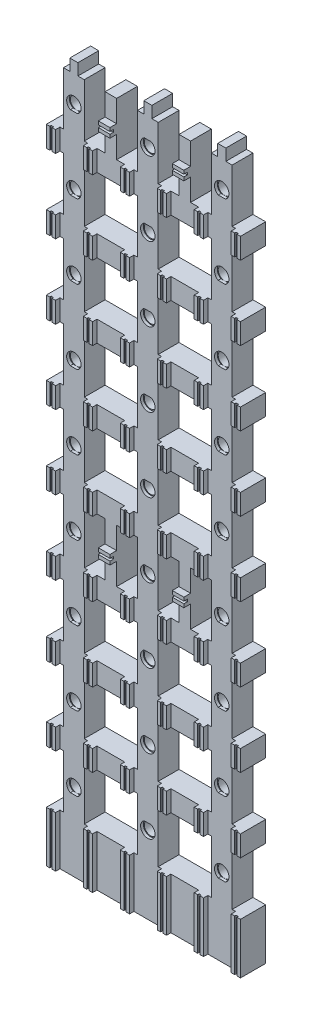
SolidWorks part; units mm, degrees
ref_plane "Front Plane" through (0, 0, 0) normal (0, 0, 1) x (1, 0, 0)
ref_plane "Top Plane" through (0, 0, 0) normal (0, 1, 0) x (1, 0, 0)
ref_plane "Right Plane" through (0, 0, 0) normal (1, 0, 0) x (0, 0, -1)
sketch "Sketch1" plane through (0, 0, 0) normal (0, 0, 1) x (1, 0, 0)
  line L1 (42, -11) -> (-42, -11)
  line L2 (42, -11) -> (42, 11)
  line L3 (42, 11) -> (-42, 11)
  line L4 (-42, -11) -> (-42, 11)
  line L5 (42, -11) -> (-42, 11) construction
  line L6 (42, 11) -> (-42, -11) construction
  point P0 (0, 0)
  dimension "D1" = 22
  dimension "D2" = 84
extrude "Boss-Extrude1" add sketch "Sketch1" along normal blind 9
sketch "Sketch2" plane through (0, 0, 9) normal (0, 0, 1) x (1, 0, 0)
  line L0 (42, 11) -> (-42, 11) construction
  line L1 (-36.5, 11) -> (-27.5, 11)
  line L2 (-36.5, 11) -> (-36.5, 295) construction
  line L3 (-36.5, 295) -> (-27.5, 295) construction
  line L4 (-27.5, 11) -> (-27.5, 295) construction
  line L5 (-42, 11) -> (-42, -11) construction
  line L6 (-33.75, 295) -> (-30.25, 295)
  line L7 (-30.25, 295) -> (-30.25, 290)
  line L8 (-30.25, 290) -> (-27.5, 290)
  line L9 (-27.5, 290) -> (-27.5, 11)
  line L10 (-36.5, 11) -> (-36.5, 290)
  line L11 (-36.5, 290) -> (-33.75, 290)
  line L12 (-33.75, 290) -> (-33.75, 295)
  point P10 (-32, 295)
  point P15 (-32, 11)
  dimension "D1" = 5.5
  dimension "D2" = 9
  dimension "D3" = 284
  dimension "D4" = 5
  dimension "D5" = 3.5
extrude "Boss-Extrude2" add sketch "Sketch2" against normal up to surface (9 mm away) up to face at (0, 0, 0)
pattern_linear "LPattern1" count 3 spacing 32 along (1, 0, 0) of "Boss-Extrude2"
sketch "Sketch3" plane through (0, 0, 9) normal (0, 0, 1) x (1, 0, 0)
  line L0 (-42, 11) -> (-42, -11) construction
  line L1 (-42, 43) -> (42, 43)
  line L2 (-42, 43) -> (-42, 34)
  line L3 (-42, 34) -> (42, 34)
  line L4 (42, 43) -> (42, 34)
  line L5 (42, -11) -> (42, 11) construction
  line L6 (-36.5, 11) -> (-42, 11) construction
  dimension "D1" = 23
  dimension "D2" = 9
extrude "Boss-Extrude3" add sketch "Sketch3" against normal up to surface (9 mm away) up to face at (0, 189.8571, 0)
pattern_linear "LPattern2" count 8 spacing 32 along (0, 1, 0) of "Boss-Extrude3"
sketch "Sketch4" plane through (0, 0, 9) normal (0, 0, 1) x (1, 0, 0)
  line L0 (-27.5, 130) -> (-4.5, 130) construction
  line L1 (-13.5, 130) -> (-18.5, 130)
  line L2 (-13.5, 130) -> (-13.5, 107)
  line L3 (-13.5, 107) -> (-18.5, 107)
  line L4 (-18.5, 130) -> (-18.5, 107)
  line L5 (-4.5, 107) -> (-27.5, 107) construction
  point P8 (-16, 107)
  dimension "D1" = 5
extrude "Boss-Extrude4" add sketch "Sketch4" against normal up to surface (9 mm away) up to face at (-16, 246.5, 0)
pattern_linear "LPattern3" count 2 spacing 32 along (1, 0, 0) count 2 spacing 160 along (0, 1, 0) of "Boss-Extrude4"
sketch "Sketch5" plane through (0, 0, 9) normal (0, 0, 1) x (1, 0, 0)
  line L0 (-36.5, 22.5) -> (-27.5, 22.5) construction
  line L1 (-36.5, 34) -> (-36.5, 11) construction
  line L2 (-27.5, 11) -> (-27.5, 34) construction
  line L3 (-4.5, 22.5) -> (4.5, 22.5) construction
  line L4 (-4.5, 34) -> (-4.5, 11) construction
  line L5 (4.5, 11) -> (4.5, 34) construction
  line L6 (27.5, 22.5) -> (36.5, 22.5) construction
  line L7 (27.5, 34) -> (27.5, 11) construction
  line L8 (36.5, 11) -> (36.5, 34) construction
  circle A0 centre (-32, 22.5) radius 2.725
  circle A1 centre (0, 22.5) radius 2.725
  circle A2 centre (32, 22.5) radius 2.725
  circle A3 centre (-32, 54.5) radius 2.725
  circle A4 centre (0, 54.5) radius 2.725
  circle A5 centre (32, 54.5) radius 2.725
  circle A6 centre (-32, 86.5) radius 2.725
  circle A7 centre (0, 86.5) radius 2.725
  circle A8 centre (32, 86.5) radius 2.725
  circle A9 centre (-32, 118.5) radius 2.725
  circle A10 centre (0, 118.5) radius 2.725
  circle A11 centre (32, 118.5) radius 2.725
  circle A12 centre (-32, 150.5) radius 2.725
  circle A13 centre (0, 150.5) radius 2.725
  circle A14 centre (32, 150.5) radius 2.725
  circle A15 centre (-32, 182.5) radius 2.725
  circle A16 centre (0, 182.5) radius 2.725
  circle A17 centre (32, 182.5) radius 2.725
  circle A18 centre (-32, 214.5) radius 2.725
  circle A19 centre (0, 214.5) radius 2.725
  circle A20 centre (32, 214.5) radius 2.725
  circle A21 centre (-32, 246.5) radius 2.725
  circle A22 centre (0, 246.5) radius 2.725
  circle A23 centre (32, 246.5) radius 2.725
  circle A24 centre (-32, 278.5) radius 2.725
  circle A25 centre (0, 278.5) radius 2.725
  circle A26 centre (32, 278.5) radius 2.725
  dimension "D1" = 5.45
  dimension "D3" = 32
  dimension "D2" = 9
extrude "Cut-Extrude1" cut sketch "Sketch5" against normal through all
sketch "Sketch6" plane through (0, 0, 9) normal (0, 0, 1) x (1, 0, 0)
  line L0 (-33.5297, 19.775) -> (-30.4703, 19.775)
  line L1 (-1.5297, 25.225) -> (1.5297, 25.225)
  line L2 (30.4703, 19.775) -> (33.5297, 19.775)
  line L3 (-33.5297, 51.775) -> (-30.4703, 51.775)
  line L4 (-1.5297, 57.225) -> (1.5297, 57.225)
  line L5 (30.4703, 51.775) -> (33.5297, 51.775)
  line L6 (-33.5297, 83.775) -> (-30.4703, 83.775)
  line L7 (-1.5297, 89.225) -> (1.5297, 89.225)
  line L8 (30.4703, 83.775) -> (33.5297, 83.775)
  line L9 (-33.5297, 115.775) -> (-30.4703, 115.775)
  line L10 (-1.5297, 121.225) -> (1.5297, 121.225)
  line L11 (30.4703, 115.775) -> (33.5297, 115.775)
  line L12 (-33.5297, 147.775) -> (-30.4703, 147.775)
  line L13 (-1.5297, 153.225) -> (1.5297, 153.225)
  line L14 (30.4703, 147.775) -> (33.5297, 147.775)
  line L15 (-33.5297, 179.775) -> (-30.4703, 179.775)
  line L16 (-1.5297, 185.225) -> (1.5297, 185.225)
  line L17 (30.4703, 179.775) -> (33.5297, 179.775)
  line L18 (-33.5297, 211.775) -> (-30.4703, 211.775)
  line L19 (-1.5297, 217.225) -> (1.5297, 217.225)
  line L20 (30.4703, 211.775) -> (33.5297, 211.775)
  line L21 (-33.5297, 243.775) -> (-30.4703, 243.775)
  line L22 (-1.5297, 249.225) -> (1.5297, 249.225)
  line L23 (30.4703, 243.775) -> (33.5297, 243.775)
  line L24 (-33.5297, 275.775) -> (-30.4703, 275.775)
  line L25 (-1.5297, 281.225) -> (1.5297, 281.225)
  line L26 (30.4703, 275.775) -> (33.5297, 275.775)
  arc A0 (-30.4703, 19.775) -> (-33.5297, 19.775) centre (-32, 22.5) ccw
  arc A1 (-1.5297, 25.225) -> (1.5297, 25.225) centre (0, 22.5) ccw
  arc A2 (33.5297, 19.775) -> (30.4703, 19.775) centre (32, 22.5) ccw
  circle A3 centre (32, 22.5) radius 2.725 construction
  circle A4 centre (0, 22.5) radius 2.725 construction
  circle A5 centre (-32, 22.5) radius 2.725 construction
  arc A6 (-30.4703, 51.775) -> (-33.5297, 51.775) centre (-32, 54.5) ccw
  arc A7 (-1.5297, 57.225) -> (1.5297, 57.225) centre (0, 54.5) ccw
  arc A8 (33.5297, 51.775) -> (30.4703, 51.775) centre (32, 54.5) ccw
  arc A9 (-30.4703, 83.775) -> (-33.5297, 83.775) centre (-32, 86.5) ccw
  arc A10 (-1.5297, 89.225) -> (1.5297, 89.225) centre (0, 86.5) ccw
  arc A11 (33.5297, 83.775) -> (30.4703, 83.775) centre (32, 86.5) ccw
  arc A12 (-30.4703, 115.775) -> (-33.5297, 115.775) centre (-32, 118.5) ccw
  arc A13 (-1.5297, 121.225) -> (1.5297, 121.225) centre (0, 118.5) ccw
  arc A14 (33.5297, 115.775) -> (30.4703, 115.775) centre (32, 118.5) ccw
  arc A15 (-30.4703, 147.775) -> (-33.5297, 147.775) centre (-32, 150.5) ccw
  arc A16 (-1.5297, 153.225) -> (1.5297, 153.225) centre (0, 150.5) ccw
  arc A17 (33.5297, 147.775) -> (30.4703, 147.775) centre (32, 150.5) ccw
  arc A18 (-30.4703, 179.775) -> (-33.5297, 179.775) centre (-32, 182.5) ccw
  arc A19 (-1.5297, 185.225) -> (1.5297, 185.225) centre (0, 182.5) ccw
  arc A20 (33.5297, 179.775) -> (30.4703, 179.775) centre (32, 182.5) ccw
  arc A21 (-30.4703, 211.775) -> (-33.5297, 211.775) centre (-32, 214.5) ccw
  arc A22 (-1.5297, 217.225) -> (1.5297, 217.225) centre (0, 214.5) ccw
  arc A23 (33.5297, 211.775) -> (30.4703, 211.775) centre (32, 214.5) ccw
  arc A24 (-30.4703, 243.775) -> (-33.5297, 243.775) centre (-32, 246.5) ccw
  arc A25 (-1.5297, 249.225) -> (1.5297, 249.225) centre (0, 246.5) ccw
  arc A26 (33.5297, 243.775) -> (30.4703, 243.775) centre (32, 246.5) ccw
  arc A27 (-30.4703, 275.775) -> (-33.5297, 275.775) centre (-32, 278.5) ccw
  arc A28 (-1.5297, 281.225) -> (1.5297, 281.225) centre (0, 278.5) ccw
  arc A29 (33.5297, 275.775) -> (30.4703, 275.775) centre (32, 278.5) ccw
  dimension "D1" = 6.25
  dimension "D3" = 32
  dimension "D2" = 9
extrude "Cut-Extrude2" cut sketch "Sketch6" against normal blind 1.2
sketch "Sketch7" plane through (0, 0, 9) normal (0, 0, 1) x (1, 0, 0)
  line L0 (-42, -11) -> (42, -11) construction
  line L1 (-42, 11) -> (-38, 11)
  line L2 (-42, 11) -> (-42, -11)
  line L3 (-42, -11) -> (-38, -11)
  line L4 (-38, 11) -> (-38, -11)
  line L5 (-36.5, 34) -> (-36.5, 11) construction
  line L11 (-26, 11) -> (-22, 11)
  line L12 (-26, 11) -> (-26, -11)
  line L13 (-26, -11) -> (-22, -11)
  line L14 (-22, 11) -> (-22, -11)
  line L15 (-10, 11) -> (-6, 11)
  line L16 (-10, 11) -> (-10, -11)
  line L17 (-10, -11) -> (-6, -11)
  line L18 (-6, 11) -> (-6, -11)
  line L19 (6, 11) -> (10, 11)
  line L20 (6, 11) -> (6, -11)
  line L21 (6, -11) -> (10, -11)
  line L22 (10, 11) -> (10, -11)
  line L23 (22, 11) -> (26, 11)
  line L24 (22, 11) -> (22, -11)
  line L25 (22, -11) -> (26, -11)
  line L26 (26, 11) -> (26, -11)
  line L27 (38, 11) -> (42, 11)
  line L28 (38, 11) -> (38, -11)
  line L29 (38, -11) -> (42, -11)
  line L30 (42, 11) -> (42, -11)
  dimension "D1" = 1.5
  dimension "D3" = 16
  dimension "D5" = 32
  dimension "D2" = 2
  dimension "D4" = 3
extrude "Boss-Extrude5" add sketch "Sketch7" along normal blind 1.9
sketch "Sketch8" plane through (0, 0, 9) normal (0, 0, 1) x (1, 0, 0)
  line L0 (-42, 34) -> (-36.5, 34) construction
  line L1 (-42, 43) -> (-38, 43)
  line L2 (-42, 43) -> (-42, 34)
  line L3 (-42, 34) -> (-38, 34)
  line L4 (-38, 43) -> (-38, 34)
  line L5 (-38, -11) -> (-38, 11) construction
  line L6 (-26, 43) -> (-22, 43)
  line L7 (-26, 43) -> (-26, 34)
  line L8 (-26, 34) -> (-22, 34)
  line L9 (-22, 43) -> (-22, 34)
  line L10 (-10, 43) -> (-6, 43)
  line L11 (-10, 43) -> (-10, 34)
  line L12 (-10, 34) -> (-6, 34)
  line L13 (-6, 43) -> (-6, 34)
  line L14 (6, 43) -> (10, 43)
  line L15 (6, 43) -> (6, 34)
  line L16 (6, 34) -> (10, 34)
  line L17 (10, 43) -> (10, 34)
  line L18 (22, 43) -> (26, 43)
  line L19 (22, 43) -> (22, 34)
  line L20 (22, 34) -> (26, 34)
  line L21 (26, 43) -> (26, 34)
  line L22 (38, 43) -> (42, 43)
  line L23 (38, 43) -> (38, 34)
  line L24 (38, 34) -> (42, 34)
  line L25 (42, 43) -> (42, 34)
  dimension "D2" = 16
  dimension "D4" = 32
  dimension "D1" = 2
  dimension "D3" = 3
extrude "Boss-Extrude6" add sketch "Sketch8" along normal up to surface (1.9 mm away) up to face at (-40, 0, 10.9)
pattern_linear "LPattern4" count 8 spacing 32 along (0, 1, 0) of "Boss-Extrude6"
sketch "Sketch9" plane through (0, 0, 10.9) normal (0, 0, 1) x (1, 0, 0)
  line L0 (-42, -11) -> (-38, -11) construction
  line L1 (-40.5, -11) -> (-39.5, -11)
  line L2 (-40.5, -11) -> (-40.5, 11)
  line L3 (-40.5, 11) -> (-39.5, 11)
  line L4 (-39.5, -11) -> (-39.5, 11)
  line L5 (-38, 11) -> (-42, 11) construction
  point P8 (-40, 11)
  dimension "D1" = 1
extrude "Cut-Extrude3" cut sketch "Sketch9" against normal blind 0.6
pattern_linear "LPattern5" count 6 spacing 16 along (1, 0, 0) count 9 spacing 32 along (0, 1, 0) of "Cut-Extrude3"
sketch "Sketch10" plane through (0, 0, 9) normal (0, 0, 1) x (1, 0, 0)
  line L0 (-18.5, 130) -> (-18.5, 107) construction
  line L1 (-18.5, 120.5) -> (-13.5, 120.5)
  line L2 (-18.5, 120.5) -> (-18.5, 116.5)
  line L3 (-18.5, 116.5) -> (-13.5, 116.5)
  line L4 (-13.5, 120.5) -> (-13.5, 116.5)
  line L5 (-13.5, 107) -> (-13.5, 130) construction
  point P8 (-18.5, 118.5)
  dimension "D1" = 4
extrude "Boss-Extrude7" add sketch "Sketch10" along normal blind 2.9
pattern_linear "LPattern6" count 2 spacing 32 along (1, 0, 0) count 2 spacing 160 along (0, 1, 0) of "Boss-Extrude7"
sketch "Sketch11" plane through (0, 0, 11.9) normal (0, 0, 1) x (1, 0, 0)
  line L0 (-18.5, 120.5) -> (-18.5, 116.5) construction
  line L1 (-18.5, 119) -> (-13.5, 119)
  line L2 (-18.5, 119) -> (-18.5, 118)
  line L3 (-18.5, 118) -> (-13.5, 118)
  line L4 (-13.5, 119) -> (-13.5, 118)
  line L5 (-13.5, 116.5) -> (-13.5, 120.5) construction
  point P8 (-18.5, 118.5)
  dimension "D1" = 1
extrude "Cut-Extrude4" cut sketch "Sketch11" against normal blind 1.5
pattern_linear "LPattern7" count 2 spacing 32 along (1, 0, 0) count 2 spacing 160 along (0, 1, 0) of "Cut-Extrude4"
